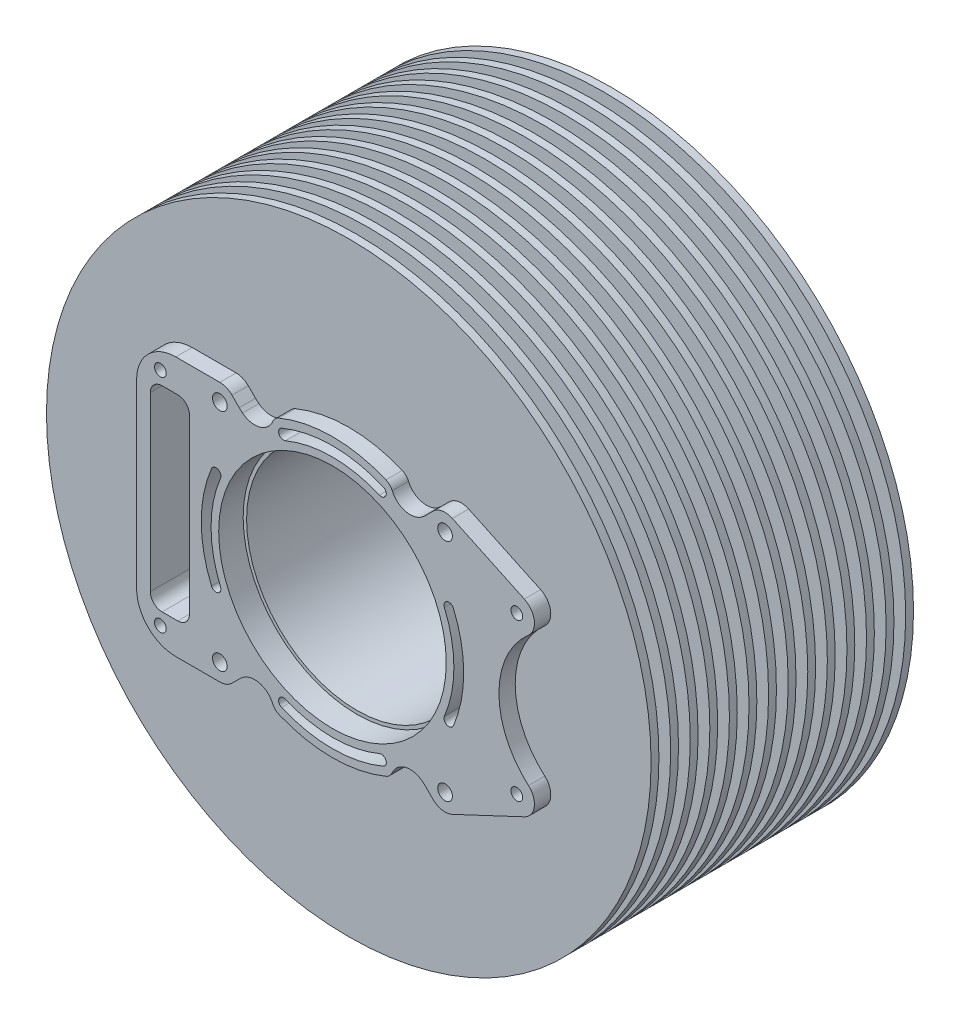
SolidWorks part; units mm, degrees
material "2024-T3"
ref_plane "Front Plane" through (0, 0, 0) normal (0, 0, 1) x (1, 0, 0)
ref_plane "Top Plane" through (0, 0, 0) normal (0, 1, 0) x (1, 0, 0)
ref_plane "Right Plane" through (0, 0, 0) normal (1, 0, 0) x (0, 0, -1)
sketch "Sketch1" plane through (0, 0, 0) normal (0, 0, 1) x (1, 0, 0)
  line L8 (-91.7539, 59.9982) -> (-95.4428, 63.6872)
  line L9 (-107.8172, 51.3128) -> (-104.1282, 47.6239)
  line L10 (-104.1282, -47.6239) -> (-107.8172, -51.3128)
  line L11 (-95.4428, -63.6872) -> (-91.7539, -59.9982)
  line L12 (3.4939, -59.9982) -> (7.1828, -63.6872)
  line L13 (19.5572, -51.3128) -> (15.8682, -47.6239)
  line L14 (15.8682, 47.6239) -> (19.5572, 51.3128)
  line L15 (7.1828, 63.6872) -> (3.4939, 59.9982)
  line L16 (-91.7539, 59.9982) -> (-95.4428, 63.6872)
  line L17 (-107.8172, 51.3128) -> (-104.1282, 47.6239)
  line L18 (-104.1282, -47.6239) -> (-107.8172, -51.3128)
  line L19 (-95.4428, -63.6872) -> (-91.7539, -59.9982)
  line L20 (3.4939, -59.9982) -> (7.1828, -63.6872)
  line L21 (19.5572, -51.3128) -> (15.8682, -47.6239)
  line L22 (15.8682, 47.6239) -> (19.5572, 51.3128)
  line L23 (7.1828, 63.6872) -> (3.4939, 59.9982)
  circle A0 centre (-101.63, -57.5) radius 3.75 construction
  circle A1 centre (13.37, -57.5) radius 3.75 construction
  circle A2 centre (13.37, 57.5) radius 3.75 construction
  circle A3 centre (-44.13, 0) radius 56.35 construction
  circle A4 centre (-101.63, 57.5) radius 3.75 construction
  circle A5 centre (-101.63, -57.5) radius 3.75
  circle A6 centre (13.37, -57.5) radius 3.75
  circle A7 centre (13.37, 57.5) radius 3.75
  circle A8 centre (-44.13, 0) radius 56.35
  circle A9 centre (-101.63, 57.5) radius 3.75
  arc A16 (-91.7539, 59.9982) -> (-90.0538, 58.4817) centre (-77.6117, 74.1404) ccw
  arc A17 (-95.4428, 63.6872) -> (-107.8172, 51.3128) centre (-101.63, 57.5) ccw
  arc A18 (-102.6117, 45.9238) -> (-104.1282, 47.6239) centre (-118.2704, 33.4817) ccw
  arc A19 (-106.4966, 30.5135) -> (-109.6685, 27.3077) centre (-104.13, 25) ccw
  arc A20 (-104.1282, -47.6239) -> (-102.6117, -45.9238) centre (-118.2704, -33.4817) ccw
  arc A21 (-107.8172, -51.3128) -> (-95.4428, -63.6872) centre (-101.63, -57.5) ccw
  arc A22 (-90.0538, -58.4817) -> (-91.7539, -59.9982) centre (-77.6117, -74.1404) ccw
  arc A23 (-106.4966, 30.5135) -> (-109.6685, 27.3077) centre (-104.13, 25) ccw
  arc A24 (3.4939, -59.9982) -> (1.7938, -58.4817) centre (-10.6483, -74.1404) ccw
  arc A25 (7.1828, -63.6872) -> (19.5572, -51.3128) centre (13.37, -57.5) ccw
  arc A26 (14.3517, -45.9238) -> (15.8682, -47.6239) centre (30.0104, -33.4817) ccw
  arc A27 (-109.6685, 27.3077) -> (-109.6685, -27.3077) centre (-44.13, 0) ccw
  arc A28 (15.8682, 47.6239) -> (14.3517, 45.9238) centre (30.0104, 33.4817) ccw
  arc A29 (19.5572, 51.3128) -> (7.1828, 63.6872) centre (13.37, 57.5) ccw
  arc A30 (1.7938, 58.4817) -> (3.4939, 59.9982) centre (-10.6483, 74.1404) ccw
  arc A31 (-109.6685, 27.3077) -> (-109.6685, -27.3077) centre (-44.13, 0) ccw
  arc A32 (-91.7539, 59.9982) -> (-90.0538, 58.4817) centre (-77.6117, 74.1404) ccw
  arc A33 (-95.4428, 63.6872) -> (-107.8172, 51.3128) centre (-101.63, 57.5) ccw
  arc A34 (-102.6117, 45.9238) -> (-104.1282, 47.6239) centre (-118.2704, 33.4817) ccw
  arc A36 (-104.1282, -47.6239) -> (-102.6117, -45.9238) centre (-118.2704, -33.4817) ccw
  arc A37 (-107.8172, -51.3128) -> (-95.4428, -63.6872) centre (-101.63, -57.5) ccw
  arc A38 (-90.0538, -58.4817) -> (-91.7539, -59.9982) centre (-77.6117, -74.1404) ccw
  arc A40 (3.4939, -59.9982) -> (1.7938, -58.4817) centre (-10.6483, -74.1404) ccw
  arc A41 (7.1828, -63.6872) -> (19.5572, -51.3128) centre (13.37, -57.5) ccw
  arc A42 (14.3517, -45.9238) -> (15.8682, -47.6239) centre (30.0104, -33.4817) ccw
  arc A44 (15.8682, 47.6239) -> (14.3517, 45.9238) centre (30.0104, 33.4817) ccw
  arc A45 (19.5572, 51.3128) -> (7.1828, 63.6872) centre (13.37, 57.5) ccw
  arc A46 (1.7938, 58.4817) -> (3.4939, 59.9982) centre (-10.6483, 74.1404) ccw
  arc A186 (-109.6685, -27.3077) -> (-106.4966, -30.5135) centre (-104.13, -25) ccw
  arc A187 (-109.6685, -27.3077) -> (-106.4966, -30.5135) centre (-104.13, -25) ccw
  arc A188 (-74.6435, -62.3666) -> (-71.4377, -65.5385) centre (-69.13, -60) ccw
  arc A189 (-74.6435, -62.3666) -> (-71.4377, -65.5385) centre (-69.13, -60) ccw
  arc A190 (-71.4377, -65.5385) -> (-16.8223, -65.5385) centre (-44.13, 0) ccw
  arc A191 (-71.4377, -65.5385) -> (-16.8223, -65.5385) centre (-44.13, 0) ccw
  arc A192 (-16.8223, -65.5385) -> (-13.6165, -62.3666) centre (-19.13, -60) ccw
  arc A193 (-16.8223, -65.5385) -> (-13.6165, -62.3666) centre (-19.13, -60) ccw
  arc A194 (18.2366, -30.5135) -> (21.4085, -27.3077) centre (15.87, -25) ccw
  arc A195 (18.2366, -30.5135) -> (21.4085, -27.3077) centre (15.87, -25) ccw
  arc A196 (21.4085, -27.3077) -> (21.4085, 27.3077) centre (-44.13, 0) ccw
  arc A197 (21.4085, -27.3077) -> (21.4085, 27.3077) centre (-44.13, 0) ccw
  arc A198 (21.4085, 27.3077) -> (18.2366, 30.5135) centre (15.87, 25) ccw
  arc A199 (21.4085, 27.3077) -> (18.2366, 30.5135) centre (15.87, 25) ccw
  arc A200 (-13.6165, 62.3666) -> (-16.8223, 65.5385) centre (-19.13, 60) ccw
  arc A201 (-13.6165, 62.3666) -> (-16.8223, 65.5385) centre (-19.13, 60) ccw
  arc A202 (-16.8223, 65.5385) -> (-71.4377, 65.5385) centre (-44.13, 0) ccw
  arc A203 (-16.8223, 65.5385) -> (-71.4377, 65.5385) centre (-44.13, 0) ccw
  arc A204 (-71.4377, 65.5385) -> (-74.6435, 62.3666) centre (-69.13, 60) ccw
  arc A205 (-71.4377, 65.5385) -> (-74.6435, 62.3666) centre (-69.13, 60) ccw
  arc A246 (-106.4966, 30.5135) -> (-102.6117, 45.9238) centre (-110.441, 39.7028) ccw
  arc A247 (-106.4966, 30.5135) -> (-102.6117, 45.9238) centre (-110.441, 39.7028) ccw
  arc A248 (-102.6117, -45.9238) -> (-106.4966, -30.5135) centre (-110.441, -39.7028) ccw
  arc A249 (-102.6117, -45.9238) -> (-106.4966, -30.5135) centre (-110.441, -39.7028) ccw
  arc A250 (-74.6435, -62.3666) -> (-90.0538, -58.4817) centre (-83.8328, -66.311) ccw
  arc A251 (-74.6435, -62.3666) -> (-90.0538, -58.4817) centre (-83.8328, -66.311) ccw
  arc A252 (1.7938, -58.4817) -> (-13.6165, -62.3666) centre (-4.4272, -66.311) ccw
  arc A253 (1.7938, -58.4817) -> (-13.6165, -62.3666) centre (-4.4272, -66.311) ccw
  arc A254 (18.2366, -30.5135) -> (14.3517, -45.9238) centre (22.181, -39.7028) ccw
  arc A255 (18.2366, -30.5135) -> (14.3517, -45.9238) centre (22.181, -39.7028) ccw
  arc A256 (14.3517, 45.9238) -> (18.2366, 30.5135) centre (22.181, 39.7028) ccw
  arc A257 (14.3517, 45.9238) -> (18.2366, 30.5135) centre (22.181, 39.7028) ccw
  arc A258 (-13.6165, 62.3666) -> (1.7938, 58.4817) centre (-4.4272, 66.311) ccw
  arc A259 (-13.6165, 62.3666) -> (1.7938, 58.4817) centre (-4.4272, 66.311) ccw
  arc A260 (-90.0538, 58.4817) -> (-74.6435, 62.3666) centre (-83.8328, 66.311) ccw
  arc A261 (-90.0538, 58.4817) -> (-74.6435, 62.3666) centre (-83.8328, 66.311) ccw
  dimension "D1" = 0
extrude "Boss-Extrude1" add sketch "Sketch1" along normal blind 142.33
sketch "Sketch2" plane through (0, 0, 142.33) normal (0, 0, 1) x (1, 0, 0)
  circle A0 centre (-44.13, 0) radius 58.1
  dimension "D1" = 116.2
extrude "Cut-Extrude1" cut sketch "Sketch2" against normal blind 12.5
sketch "Sketch4" plane through (0, 0, 0) normal (0, 0, 1) x (1, 0, 0)
  line L0 (-104.1282, -47.6239) -> (-107.8172, -51.3128) construction
  line L1 (-107.8172, 51.3128) -> (-104.1282, 47.6239) construction
  line L2 (-104.1282, -47.6239) -> (-107.8172, -51.3128)
  line L3 (-107.8172, 51.3128) -> (-104.1282, 47.6239)
  line L4 (-101.63, 66.25) -> (-124.13, 66.25)
  line L5 (-144.13, 46.25) -> (-144.13, -46.25)
  line L6 (-124.13, -66.25) -> (-101.63, -66.25)
  line L8 (-131.13, 50) -> (-123.13, 50)
  line L9 (-137.13, 44) -> (-137.13, -44)
  line L10 (-131.13, -50) -> (-123.13, -50)
  line L11 (-117.13, 44) -> (-117.13, -44)
  arc A0 (-107.8172, -51.3128) -> (-95.4428, -63.6872) centre (-101.63, -57.5) ccw construction
  arc A1 (-104.1282, -47.6239) -> (-102.6117, -45.9238) centre (-118.2704, -33.4817) ccw construction
  arc A3 (-95.4428, 63.6872) -> (-107.8172, 51.3128) centre (-101.63, 57.5) ccw construction
  arc A4 (-102.6117, 45.9238) -> (-104.1282, 47.6239) centre (-118.2704, 33.4817) ccw construction
  arc A5 (-107.8172, -51.3128) -> (-101.63, -66.25) centre (-101.63, -57.5) ccw
  arc A6 (-104.1282, -47.6239) -> (-102.6117, -45.9238) centre (-118.2704, -33.4817) ccw
  arc A8 (-101.63, 66.25) -> (-107.8172, 51.3128) centre (-101.63, 57.5) ccw
  arc A9 (-102.6117, 45.9238) -> (-104.1282, 47.6239) centre (-118.2704, 33.4817) ccw
  arc A10 (-123.13, -50) -> (-117.13, -44) centre (-123.13, -44) ccw
  arc A11 (-137.13, -44) -> (-131.13, -50) centre (-131.13, -44) ccw
  arc A12 (-123.13, 50) -> (-117.13, 44) centre (-123.13, 44) cw
  arc A13 (-131.13, 50) -> (-137.13, 44) centre (-131.13, 44) ccw
  arc A14 (-144.13, -46.25) -> (-124.13, -66.25) centre (-124.13, -46.25) ccw
  arc A15 (-124.13, 66.25) -> (-144.13, 46.25) centre (-124.13, 46.25) ccw
  arc A16 (-106.4966, 30.5135) -> (-102.6117, 45.9238) centre (-110.441, 39.7028) ccw construction
  arc A17 (-106.4966, 30.5135) -> (-102.6117, 45.9238) centre (-110.441, 39.7028) ccw
  arc A18 (-106.4966, 30.5135) -> (-109.6685, 27.3077) centre (-104.13, 25) ccw construction
  arc A19 (-106.4966, 30.5135) -> (-109.6685, 27.3077) centre (-104.13, 25) ccw
  arc A20 (-102.6117, -45.9238) -> (-106.4966, -30.5135) centre (-110.441, -39.7028) ccw construction
  arc A21 (-109.6685, -27.3077) -> (-106.4966, -30.5135) centre (-104.13, -25) ccw construction
  arc A22 (-109.6685, 27.3077) -> (-109.6685, -27.3077) centre (-44.13, 0) ccw construction
  arc A23 (-102.6117, -45.9238) -> (-106.4966, -30.5135) centre (-110.441, -39.7028) ccw
  arc A24 (-109.6685, -27.3077) -> (-106.4966, -30.5135) centre (-104.13, -25) ccw
  arc A25 (-109.6685, 27.3077) -> (-109.6685, -27.3077) centre (-44.13, 0) ccw
  point P27 (-117.13, 50)
  point P30 (-137.13, 50)
  point P35 (-137.13, 0)
  point P36 (-144.13, 0)
  dimension "D3" = 6
  dimension "D4" = 20
  dimension "D1" = 100
  dimension "D2" = 20
  dimension "D5" = 100
  dimension "D6" = 7
extrude "Boss-Extrude2" add sketch "Sketch4" along normal blind 142.33
sketch "Sketch5" plane through (0, 0, 0) normal (0, 0, 1) x (1, 0, 0)
  line L0 (-101.63, 66.25) -> (-124.13, 66.25) construction
  line L1 (-91.7539, 59.9982) -> (-95.4428, 63.6872) construction
  line L2 (7.1828, 63.6872) -> (3.4939, 59.9982) construction
  line L3 (15.8682, 47.6239) -> (19.5572, 51.3128) construction
  line L4 (19.5572, -51.3128) -> (15.8682, -47.6239) construction
  line L5 (3.4939, -59.9982) -> (7.1828, -63.6872) construction
  line L6 (-95.4428, -63.6872) -> (-91.7539, -59.9982) construction
  line L7 (-124.13, -66.25) -> (-101.63, -66.25) construction
  line L8 (-144.13, 46.25) -> (-144.13, -46.25) construction
  line L9 (-101.63, 66.25) -> (-124.13, 66.25)
  line L10 (-91.7539, 59.9982) -> (-95.4428, 63.6872)
  line L11 (7.1828, 63.6872) -> (3.4939, 59.9982)
  line L12 (15.8682, 47.6239) -> (19.5572, 51.3128)
  line L13 (19.5572, -51.3128) -> (15.8682, -47.6239)
  line L14 (3.4939, -59.9982) -> (7.1828, -63.6872)
  line L15 (-95.4428, -63.6872) -> (-91.7539, -59.9982)
  line L16 (-124.13, -66.25) -> (-101.63, -66.25)
  line L17 (-144.13, 46.25) -> (-144.13, -46.25)
  line L18 (-131.13, -50) -> (-123.13, -50) construction
  line L19 (-137.13, 44) -> (-137.13, -44) construction
  line L20 (-123.13, 50) -> (-131.13, 50) construction
  line L21 (-117.13, -44) -> (-117.13, 44) construction
  line L22 (-131.13, -50) -> (-123.13, -50)
  line L23 (-137.13, 44) -> (-137.13, -44)
  line L24 (-123.13, 50) -> (-131.13, 50)
  line L25 (-117.13, -44) -> (-117.13, 44)
  arc A0 (-95.4428, 63.6872) -> (-101.63, 66.25) centre (-101.63, 57.5) ccw construction
  arc A1 (-91.7539, 59.9982) -> (-90.0538, 58.4817) centre (-77.6117, 74.1404) ccw construction
  arc A3 (1.7938, 58.4817) -> (3.4939, 59.9982) centre (-10.6483, 74.1404) ccw construction
  arc A4 (19.5572, 51.3128) -> (7.1828, 63.6872) centre (13.37, 57.5) ccw construction
  arc A5 (15.8682, 47.6239) -> (14.3517, 45.9238) centre (30.0104, 33.4817) ccw construction
  arc A7 (14.3517, -45.9238) -> (15.8682, -47.6239) centre (30.0104, -33.4817) ccw construction
  arc A8 (7.1828, -63.6872) -> (19.5572, -51.3128) centre (13.37, -57.5) ccw construction
  arc A9 (3.4939, -59.9982) -> (1.7938, -58.4817) centre (-10.6483, -74.1404) ccw construction
  arc A11 (-90.0538, -58.4817) -> (-91.7539, -59.9982) centre (-77.6117, -74.1404) ccw construction
  arc A12 (-101.63, -66.25) -> (-95.4428, -63.6872) centre (-101.63, -57.5) ccw construction
  arc A13 (-144.13, -46.25) -> (-124.13, -66.25) centre (-124.13, -46.25) ccw construction
  arc A14 (-124.13, 66.25) -> (-144.13, 46.25) centre (-124.13, 46.25) ccw construction
  arc A15 (-95.4428, 63.6872) -> (-101.63, 66.25) centre (-101.63, 57.5) ccw
  arc A16 (-91.7539, 59.9982) -> (-90.0538, 58.4817) centre (-77.6117, 74.1404) ccw
  arc A18 (1.7938, 58.4817) -> (3.4939, 59.9982) centre (-10.6483, 74.1404) ccw
  arc A19 (19.5572, 51.3128) -> (7.1828, 63.6872) centre (13.37, 57.5) ccw
  arc A20 (15.8682, 47.6239) -> (14.3517, 45.9238) centre (30.0104, 33.4817) ccw
  arc A22 (14.3517, -45.9238) -> (15.8682, -47.6239) centre (30.0104, -33.4817) ccw
  arc A23 (7.1828, -63.6872) -> (19.5572, -51.3128) centre (13.37, -57.5) ccw
  arc A24 (3.4939, -59.9982) -> (1.7938, -58.4817) centre (-10.6483, -74.1404) ccw
  arc A26 (-90.0538, -58.4817) -> (-91.7539, -59.9982) centre (-77.6117, -74.1404) ccw
  arc A27 (-101.63, -66.25) -> (-95.4428, -63.6872) centre (-101.63, -57.5) ccw
  arc A28 (-144.13, -46.25) -> (-124.13, -66.25) centre (-124.13, -46.25) ccw
  arc A29 (-124.13, 66.25) -> (-144.13, 46.25) centre (-124.13, 46.25) ccw
  arc A30 (-123.13, -50) -> (-117.13, -44) centre (-123.13, -44) ccw construction
  arc A31 (-137.13, -44) -> (-131.13, -50) centre (-131.13, -44) ccw construction
  arc A32 (-131.13, 50) -> (-137.13, 44) centre (-131.13, 44) ccw construction
  arc A33 (-117.13, 44) -> (-123.13, 50) centre (-123.13, 44) ccw construction
  circle A34 centre (13.37, -57.5) radius 3.75 construction
  circle A35 centre (-101.63, -57.5) radius 3.75 construction
  circle A36 centre (13.37, 57.5) radius 3.75 construction
  circle A37 centre (-101.63, 57.5) radius 3.75 construction
  arc A38 (-123.13, -50) -> (-117.13, -44) centre (-123.13, -44) ccw
  arc A39 (-137.13, -44) -> (-131.13, -50) centre (-131.13, -44) ccw
  arc A40 (-131.13, 50) -> (-137.13, 44) centre (-131.13, 44) ccw
  arc A41 (-117.13, 44) -> (-123.13, 50) centre (-123.13, 44) ccw
  circle A42 centre (13.37, -57.5) radius 3.75
  circle A43 centre (-101.63, -57.5) radius 3.75
  circle A44 centre (13.37, 57.5) radius 3.75
  circle A45 centre (-101.63, 57.5) radius 3.75
  circle A46 centre (-44.13, 0) radius 56.35 construction
  circle A47 centre (-44.13, 0) radius 56.35
  circle A48 centre (-44.13, 0) radius 154.3579
  arc A49 (-90.0538, 58.4817) -> (-74.6435, 62.3666) centre (-83.8328, 66.311) ccw construction
  arc A50 (-71.4377, 65.5385) -> (-74.6435, 62.3666) centre (-69.13, 60) ccw construction
  arc A51 (-16.8223, 65.5385) -> (-71.4377, 65.5385) centre (-44.13, 0) ccw construction
  arc A52 (-13.6165, 62.3666) -> (-16.8223, 65.5385) centre (-19.13, 60) ccw construction
  arc A53 (-13.6165, 62.3666) -> (1.7938, 58.4817) centre (-4.4272, 66.311) ccw construction
  arc A54 (18.2366, -30.5135) -> (21.4085, -27.3077) centre (15.87, -25) ccw construction
  arc A55 (18.2366, -30.5135) -> (14.3517, -45.9238) centre (22.181, -39.7028) ccw construction
  arc A56 (21.4085, -27.3077) -> (21.4085, 27.3077) centre (-44.13, 0) ccw construction
  arc A57 (21.4085, 27.3077) -> (18.2366, 30.5135) centre (15.87, 25) ccw construction
  arc A58 (14.3517, 45.9238) -> (18.2366, 30.5135) centre (22.181, 39.7028) ccw construction
  arc A59 (-16.8223, -65.5385) -> (-13.6165, -62.3666) centre (-19.13, -60) ccw construction
  arc A60 (1.7938, -58.4817) -> (-13.6165, -62.3666) centre (-4.4272, -66.311) ccw construction
  arc A61 (-71.4377, -65.5385) -> (-16.8223, -65.5385) centre (-44.13, 0) ccw construction
  arc A62 (-74.6435, -62.3666) -> (-71.4377, -65.5385) centre (-69.13, -60) ccw construction
  arc A63 (-74.6435, -62.3666) -> (-90.0538, -58.4817) centre (-83.8328, -66.311) ccw construction
  arc A64 (-90.0538, 58.4817) -> (-74.6435, 62.3666) centre (-83.8328, 66.311) ccw
  arc A65 (-71.4377, 65.5385) -> (-74.6435, 62.3666) centre (-69.13, 60) ccw
  arc A66 (-16.8223, 65.5385) -> (-71.4377, 65.5385) centre (-44.13, 0) ccw
  arc A67 (-13.6165, 62.3666) -> (-16.8223, 65.5385) centre (-19.13, 60) ccw
  arc A68 (-13.6165, 62.3666) -> (1.7938, 58.4817) centre (-4.4272, 66.311) ccw
  arc A69 (18.2366, -30.5135) -> (21.4085, -27.3077) centre (15.87, -25) ccw
  arc A70 (18.2366, -30.5135) -> (14.3517, -45.9238) centre (22.181, -39.7028) ccw
  arc A71 (21.4085, -27.3077) -> (21.4085, 27.3077) centre (-44.13, 0) ccw
  arc A72 (21.4085, 27.3077) -> (18.2366, 30.5135) centre (15.87, 25) ccw
  arc A73 (14.3517, 45.9238) -> (18.2366, 30.5135) centre (22.181, 39.7028) ccw
  arc A74 (-16.8223, -65.5385) -> (-13.6165, -62.3666) centre (-19.13, -60) ccw
  arc A75 (1.7938, -58.4817) -> (-13.6165, -62.3666) centre (-4.4272, -66.311) ccw
  arc A76 (-71.4377, -65.5385) -> (-16.8223, -65.5385) centre (-44.13, 0) ccw
  arc A77 (-74.6435, -62.3666) -> (-71.4377, -65.5385) centre (-69.13, -60) ccw
  arc A78 (-74.6435, -62.3666) -> (-90.0538, -58.4817) centre (-83.8328, -66.311) ccw
extrude "Boss-Extrude3" add sketch "Sketch5" along normal blind 4 contours A48 A29 L9 A15 L10 A16 A18 L11 A19 L12 A20 A22 L13 A23 L14 A24 A26 L15 A27 L16 A28 L17 region at (-194.122, 0, 0)
pattern_linear "LPattern1" count 14 spacing 10 along (0, 0, 1) of "Boss-Extrude3"
sketch "Sketch6" plane through (0, 0, 142.33) normal (0, 0, 1) x (1, 0, 0)
  line L0 (-103.588, 25) -> (-103.588, -25) construction
  circle A0 centre (-44.13, 0) radius 62
  circle A1 centre (-44.13, 0) radius 67
  arc A2 (-105.8925, 25.969) -> (-101.2834, 24.031) centre (-103.588, 25) cw
  arc A3 (-105.8925, -25.969) -> (-101.2834, -24.031) centre (-103.588, -25) ccw
  arc A4 (-70.099, 61.7625) -> (-68.161, 57.1534) centre (-69.13, 59.458) ccw
  arc A5 (-18.161, 61.7625) -> (-20.099, 57.1534) centre (-19.13, 59.458) cw
  arc A6 (17.6325, 25.969) -> (13.0234, 24.031) centre (15.328, 25) ccw
  arc A7 (17.6325, -25.969) -> (13.0234, -24.031) centre (15.328, -25) cw
  arc A8 (-18.161, -61.7625) -> (-20.099, -57.1534) centre (-19.13, -59.458) ccw
  arc A9 (-70.099, -61.7625) -> (-68.161, -57.1534) centre (-69.13, -59.458) cw
  circle A10 centre (-44.13, 0) radius 56.35 construction
  point P11 (-103.588, 0)
  point P33 (-44.13, 0)
  dimension "D1" = 124
  dimension "D3" = 50
  dimension "D2" = 5
  dimension "D4" = 4
extrude "Cut-Extrude5" cut sketch "Sketch6" against normal through all both and the other way through all contours A9 A1 A8 A0 | A7 A1 A6 A0 | A5 A1 A4 A0 | A1 A3 A0 A2 region at (18.4422, 0, 142.33) region at (-44.13, 62.5722, 142.33) region at (-44.13, -62.5722, 142.33) region at (-106.7022, 0, 142.33)
sketch "Sketch9" plane through (0, 0, 142.33) normal (0, 0, 1) x (1, 0, 0)
  line L0 (50, -40) -> (50, 40) construction
  line L1 (0, 0) -> (50, 0) construction
  line L2 (17.0933, 65.4183) -> (53.8296, 48.1446)
  line L3 (53.8296, -48.1446) -> (17.0933, -65.4183)
  line L4 (15.8682, 47.6239) -> (19.5572, 51.3128) construction
  line L5 (19.5572, -51.3128) -> (15.8682, -47.6239) construction
  line L6 (15.8682, 47.6239) -> (19.5572, 51.3128)
  line L7 (19.5572, -51.3128) -> (15.8682, -47.6239)
  circle A0 centre (50, 40) radius 3
  circle A1 centre (50, -40) radius 3
  circle A2 centre (50, 40) radius 9
  circle A3 centre (50, -40) radius 9
  arc A5 (7.1828, -63.6872) -> (19.5572, -51.3128) centre (13.37, -57.5) ccw construction
  arc A6 (19.5572, 51.3128) -> (7.1828, 63.6872) centre (13.37, 57.5) ccw construction
  arc A7 (14.3517, 45.9238) -> (18.2366, 30.5135) centre (22.181, 39.7028) ccw construction
  arc A8 (21.4085, 27.3077) -> (18.2366, 30.5135) centre (15.87, 25) ccw construction
  arc A9 (21.4085, -27.3077) -> (21.4085, 27.3077) centre (-44.13, 0) ccw construction
  arc A10 (18.2366, -30.5135) -> (21.4085, -27.3077) centre (15.87, -25) ccw construction
  arc A11 (18.2366, -30.5135) -> (14.3517, -45.9238) centre (22.181, -39.7028) ccw construction
  arc A12 (7.1828, -63.6872) -> (19.5572, -51.3128) centre (13.37, -57.5) ccw construction
  arc A13 (19.5572, 51.3128) -> (17.0933, 65.4183) centre (13.37, 57.5) ccw
  arc A14 (14.3517, 45.9238) -> (18.2366, 30.5135) centre (22.181, 39.7028) ccw
  arc A15 (21.4085, 27.3077) -> (18.2366, 30.5135) centre (15.87, 25) ccw
  arc A16 (21.4085, -27.3077) -> (21.4085, 27.3077) centre (-44.13, 0) ccw
  arc A17 (18.2366, -30.5135) -> (21.4085, -27.3077) centre (15.87, -25) ccw
  arc A18 (18.2366, -30.5135) -> (14.3517, -45.9238) centre (22.181, -39.7028) ccw
  arc A19 (17.0933, -65.4183) -> (19.5572, -51.3128) centre (13.37, -57.5) ccw
  arc A20 (55.9265, -33.2268) -> (55.9265, 33.2268) centre (85, 0) cw
  arc A21 (15.8682, 47.6239) -> (14.3517, 45.9238) centre (30.0104, 33.4817) ccw construction
  arc A22 (15.8682, 47.6239) -> (14.3517, 45.9238) centre (30.0104, 33.4817) ccw
  arc A23 (14.3517, -45.9238) -> (15.8682, -47.6239) centre (30.0104, -33.4817) ccw construction
  arc A24 (14.3517, -45.9238) -> (15.8682, -47.6239) centre (30.0104, -33.4817) ccw
  arc A25 (7.1828, -63.6872) -> (17.0933, -65.4183) centre (13.37, -57.5) ccw construction
  arc A26 (17.0933, 65.4183) -> (7.1828, 63.6872) centre (13.37, 57.5) ccw construction
  dimension "D1" = 6
  dimension "D2" = 80
  dimension "D3" = 50
  dimension "D5" = 35
  dimension "D4" = 6
extrude "Boss-Extrude5" add sketch "Sketch9" against normal blind 40 contours A18 A24 L7 A19 L3 A3 A20 A2 L2 A13 L6 A22 A14 A15 A16 A17 | A2 A0 | A3 A1 region at (31.8015, 0, 142.33) region at (57.3833, 44.6871, 142.33) region at (57.9639, -36.3862, 142.33)
sketch "Sketch10" plane through (0, 0, 142.33) normal (0, 0, 1) x (1, 0, 0)
  line L0 (0, 0) -> (-132, 0) construction
  line L1 (-132, -56.5) -> (-132, 56.5) construction
  circle A0 centre (-132, 56.5) radius 3
  circle A1 centre (-132, -56.5) radius 3
  point P6 (-132, 0)
  dimension "D1" = 6
  dimension "D2" = 113
  dimension "D3" = 132
extrude "Cut-Extrude6" cut sketch "Sketch10" against normal blind 40
sketch "Sketch3" plane through (0, 0, 0) normal (0, 0, 1) x (1, 0, 0)
  circle A0 centre (-44.13, 0) radius 171.35
  arc A1 (-18.8798, 55.9129) -> (-69.3802, 55.9129) centre (-44.13, 0) ccw construction
  circle A2 centre (-44.13, 0) radius 56.35 construction
  circle A3 centre (-101.63, -57.5) radius 3.75 construction
  circle A4 centre (13.37, -57.5) radius 3.75 construction
  circle A5 centre (13.37, 57.5) radius 3.75 construction
  circle A6 centre (-101.63, 57.5) radius 3.75 construction
  circle A7 centre (-44.13, 0) radius 56.35
  circle A8 centre (-101.63, -57.5) radius 3.75
  circle A9 centre (13.37, -57.5) radius 3.75
  circle A10 centre (13.37, 57.5) radius 3.75
  circle A11 centre (-101.63, 57.5) radius 3.75
  dimension "D1" = 110
equation "\"Cylinder Length\"= 169.33"
equation "\"Liner Offset\"= 27"
equation "\"D1@Boss-Extrude1\"=\"Cylinder Length\"-\"Liner Offset\""
equation "\"D1@Sketch2\"=118.2-2"
equation "\"f\"= 118.2 + 2"
